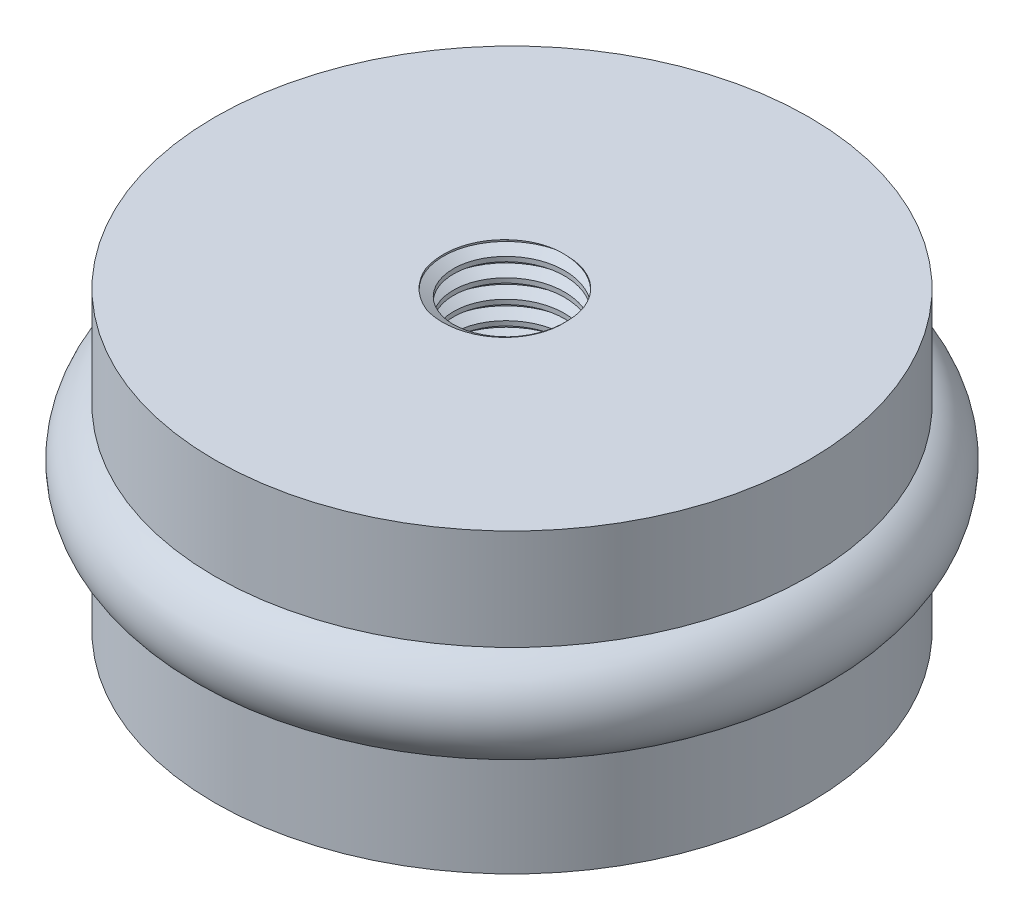
SolidWorks part; units mm, degrees
ref_plane "Front Plane" through (0, 0, 0) normal (0, 0, 1) x (1, 0, 0)
ref_plane "Top Plane" through (0, 0, 0) normal (0, 1, 0) x (1, 0, 0)
ref_plane "Right Plane" through (0, 0, 0) normal (1, 0, 0) x (0, 0, -1)
sketch "Sketch14" plane through (0, 0, 0) normal (0, 1, 0) x (1, 0, 0)
  circle A0 centre (0, 0) radius 6.75
  dimension "D1" = 13.5
extrude "Boss-Extrude2" add sketch "Sketch14" along normal mid plane 1.5
sketch "Sketch15" plane through (0, 0.75, 0) normal (0, 1, 0) x (1, 0, 0)
  circle A0 centre (0, 0) radius 8
  dimension "D1" = 16
extrude "Boss-Extrude3" add sketch "Sketch15" along normal blind 3.25
mirror "Mirror1" about plane through (0, 0, 0) normal (0, 1, 0) of "Boss-Extrude3"
sketch "Sketch16" plane through (0, 0, 0) normal (0, 0, 1) x (1, 0, 0)
  line L0 (0, 4) -> (0, -1.8259)
  line L1 (8, 4) -> (-8, 4) construction
  circle A0 centre (-7.5065, 0) radius 0.375
  dimension "D1" = 0.75
  dimension "D2" = 7.5065
  dimension "D3" = 1.8259
revolve "Revolve-Thin9" add sketch "Sketch16" angle 360 about L0
sketch "Sketch20" plane through (0, 4, 0) normal (0, 1, 0) x (1, 0, 0)
  circle A0 centre (0, 0) radius 1.5
  dimension "D1" = 3
extrude "Cut-Extrude1" cut sketch "Sketch20" against normal through all both and the other way through all
thread "Thread1" pitch 0.5 start angle 0, offset 0, length 8, pitch 0.5, diameter 3
ref_plane "Plane1" through (1.5, -4, 0) normal (0, 0, 1) x (1, 0, 0)
sketch "Thread Profile1" plane through (1.5, -4, 0) normal (0, 0, 1) x (1, 0, 0)
  line L0 (0, 0) -> (0, 0.5) construction
  line L1 (0, 0) -> (0.2706, 0.1562)
  line L2 (0.2706, 0.1562) -> (0.2706, 0.2187)
  line L3 (0.2706, 0.2187) -> (0, 0.375)
  line L4 (0.2706, 0.1875) -> (0, 0.1875) construction
  line L11 (0, 0) -> (0, 0.375)
  point P2 (0, 0)
  dimension "Pitch" = 0.5
  dimension "Profile_Angle" = 60
  dimension "Profile_Land" = 0.0625
  dimension "Profile_Height" = 0.2706
